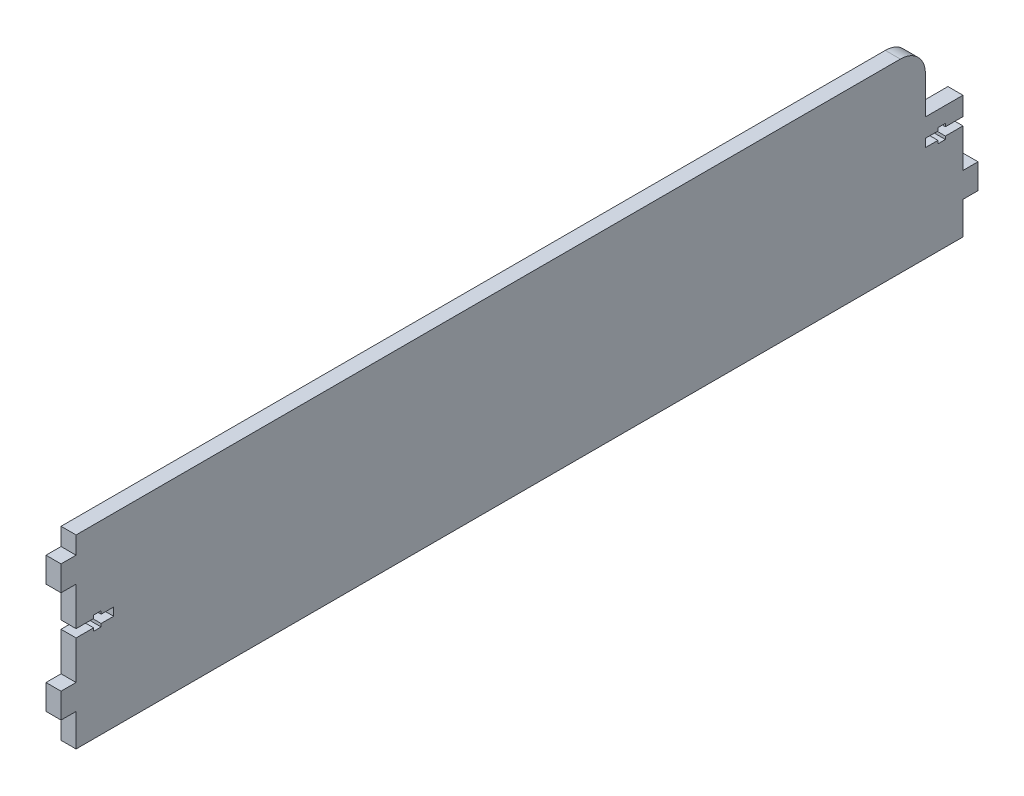
SolidWorks part; units mm, degrees
ref_plane "Front Plane" through (0, 0, 0) normal (0, 0, 1) x (1, 0, 0)
ref_plane "Top Plane" through (0, 0, 0) normal (0, 1, 0) x (1, 0, 0)
ref_plane "Right Plane" through (0, 0, 0) normal (1, 0, 0) x (0, 0, -1)
sketch "Sketch1" plane through (0, 0, 0) normal (1, 0, 0) x (0, 0, -1)
  line L1 (-177, -40) -> (177, -40)
  line L2 (-177, -40) -> (-177, 40)
  line L3 (-177, 40) -> (177, 40)
  line L4 (177, -40) -> (177, 40)
  line L5 (-177, -40) -> (177, 40) construction
  line L6 (-177, 40) -> (177, -40) construction
  point P0 (0, 0)
  dimension "D1" = 80
  dimension "D2" = 354
extrude "Boss-Extrude1" add sketch "Sketch1" along normal blind 6
sketch "Sketch4" plane through (0, 0, 177) normal (0, 0, 1) x (1, 0, 0)
  line L1 (6, 27) -> (0, 27) construction
  line L2 (6, 17) -> (6, 27) construction
  line L3 (0, 27) -> (0, 17) construction
  line L4 (0, 17) -> (6, 17) construction
  line L7 (6, -17) -> (0, -17) construction
  line L8 (6, -27) -> (6, -17) construction
  line L9 (0, -17) -> (0, -27) construction
  line L10 (0, -27) -> (6, -27) construction
  line L13 (6, 27) -> (0, 27)
  line L14 (6, 17) -> (6, 27)
  line L15 (0, 27) -> (0, 17)
  line L16 (0, 17) -> (6, 17)
  line L17 (6, -17) -> (0, -17)
  line L18 (6, -27) -> (6, -17)
  line L19 (0, -17) -> (0, -27)
  line L20 (0, -27) -> (6, -27)
extrude "Boss-Extrude2" add sketch "Sketch4" along normal blind 6
sketch "Sketch5" plane through (0, 0, 0) normal (-1, 0, 0) x (0, 0, 1)
  line L0 (177, 17) -> (177, -17) construction
  line L7 (0, 0) -> (0, -20.5925) construction
  line L8 (-177, 1.6) -> (-170, 1.6)
  line L9 (-167, 2.8) -> (-170, 2.8)
  line L10 (-167, 1.6) -> (-162, 1.6)
  line L11 (-162, -1.6) -> (-162, 1.6)
  line L12 (-167, -1.6) -> (-162, -1.6)
  line L13 (-167, -2.8) -> (-170, -2.8)
  line L14 (-177, -1.6) -> (-170, -1.6)
  line L15 (-170, -2.8) -> (-170, -1.6)
  line L16 (-170, 1.6) -> (-170, 2.8)
  line L17 (-167, 1.6) -> (-167, 2.8)
  line L18 (-167, -2.8) -> (-167, -1.6)
  line L19 (183, -1.6) -> (183, 1.6) construction
  line L20 (183, -1.6) -> (183, 1.6)
  line L21 (183, 0) -> (146.4296, 0) construction
  line L25 (177, -1.6) -> (177, 1.6)
  line L26 (167, -2.8) -> (167, -1.6)
  line L27 (167, 1.6) -> (167, 2.8)
  line L28 (170, 1.6) -> (170, 2.8)
  line L29 (170, -2.8) -> (170, -1.6)
  line L30 (177, -1.6) -> (170, -1.6)
  line L31 (167, -2.8) -> (170, -2.8)
  line L32 (167, -1.6) -> (162, -1.6)
  line L33 (162, -1.6) -> (162, 1.6)
  line L34 (167, 1.6) -> (162, 1.6)
  line L35 (167, 2.8) -> (170, 2.8)
  line L36 (177, 1.6) -> (170, 1.6)
  line L37 (-177, -1.6) -> (-177, 1.6)
  line L38 (-183, -1.6) -> (-183, 1.6)
  point P0 (177, 0)
  dimension "D1" = 15
  dimension "D2" = 5.6
  dimension "D3" = 3.2
  dimension "D4" = 7
  dimension "D5" = 3
extrude "Cut-Extrude3" cut sketch "Sketch5" against normal up to next contours L25 L36 L28 L35 L27 L34 L33 L32 L26 L31 L29 L30 | L37 L14 L15 L13 L18 L12 L11 L10 L17 L9 L16 L8 region at (0, 0, -169.3696) region at (0, 0, 169.3696)
sketch "Sketch7" plane through (0, 0, -177) normal (0, 0, -1) x (-1, 0, 0)
  line L6 (-6, -17) -> (0, -17)
  line L7 (-6, -17) -> (-6, -27)
  line L8 (-6, -27) -> (0, -27)
  line L9 (0, -17) -> (0, -27)
  line L15 (-6, -40) -> (-6, -1.6) construction
  line L16 (0, -40) -> (0, -1.6) construction
  line L17 (-6, -17) -> (0, -17) construction
  line L18 (0, -27) -> (-6, -27) construction
extrude "Boss-Extrude3" add sketch "Sketch7" along normal blind 6
sketch "Sketch8" plane through (0, 40, 0) normal (0, 1, 0) x (1, 0, 0)
  line L1 (0, 177) -> (6, 177)
  line L2 (0, 177) -> (0, -177)
  line L3 (0, -177) -> (6, -177)
  line L4 (6, 177) -> (6, -177)
extrude "Cut-Extrude4" cut sketch "Sketch8" against normal blind 6
sketch "Sketch9" plane through (0, 34, 0) normal (0, 1, 0) x (1, 0, 0)
  line L0 (0, 177) -> (0, -177) construction
  line L1 (0, 177) -> (6, 177)
  line L2 (0, 177) -> (0, 162)
  line L3 (0, 162) -> (6, 162)
  line L4 (6, 177) -> (6, 162)
  line L5 (6, -177) -> (6, 177) construction
  point P8 (6, 177)
  dimension "D2" = 15
extrude "Cut-Extrude5" cut sketch "Sketch9" against normal blind 25
fillet "Fillet1" radius 10 1 edges at (3, 34, -162)
